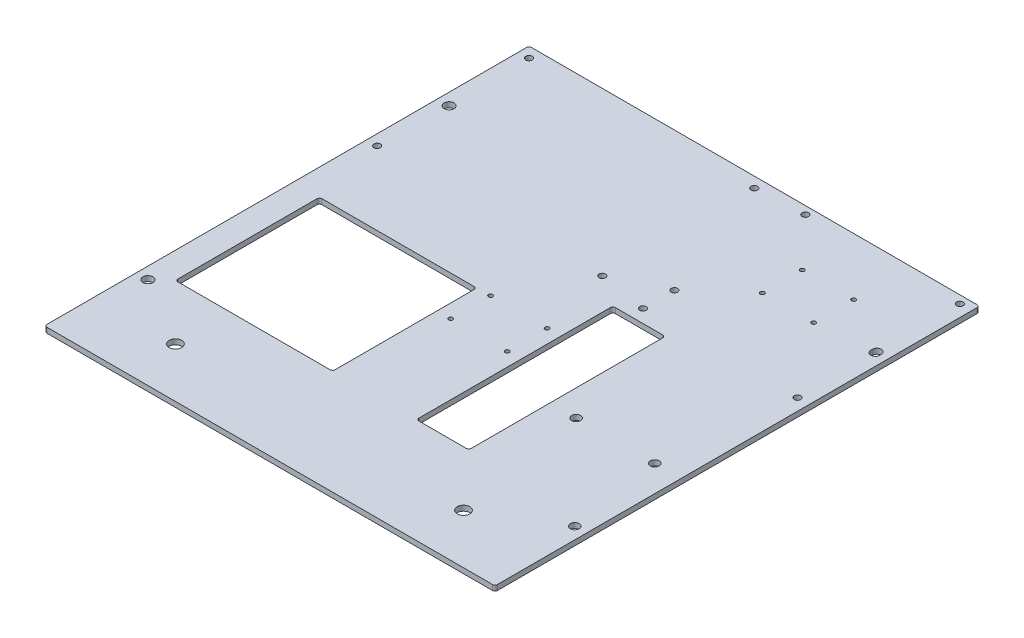
SolidWorks part; units mm, degrees
material "3.3535 (EN-AW 5154A)"
ref_plane "Ebene vorne" through (0, 0, 0) normal (0, 0, 1) x (1, 0, 0)
ref_plane "Ebene oben" through (0, 0, 0) normal (0, 1, 0) x (1, 0, 0)
ref_plane "Ebene rechts" through (0, 0, 0) normal (1, 0, 0) x (0, 0, -1)
sketch "Skizze1" plane through (0, 0, 0) normal (0, 1, 0) x (1, 0, 0)
  line L0 (-86, -92.5) -> (86, 92.5) construction
  line L1 (-86, 92.5) -> (86, 92.5)
  line L2 (-86, 92.5) -> (-86, -92.5)
  line L3 (-86, -92.5) -> (86, -92.5)
  line L4 (86, 92.5) -> (86, -92.5)
  point P4 (0, 0)
  dimension "D1" = 172
  dimension "D2" = 185
extrude "Aufsatz-Linear austragen1" add sketch "Skizze1" along normal blind 2
hole_wizard "Durchgangsloch für M31" positions "Skizze4" profile "Skizze3" hole size "M3" standard "ANSI Metrisch" end condition through all
sketch "Skizze4" plane through (0, 2, 0) normal (0, 1, 0) x (1, 0, 0)
  line L1 (-81.5, 57.5) -> (81.5, 57.5)
  line L2 (-81.5, 57.5) -> (-81.5, -57.5)
  line L3 (-81.5, -57.5) -> (81.5, -57.5)
  line L4 (81.5, 57.5) -> (81.5, -57.5)
  line L5 (86, 92.5) -> (-86, 92.5) construction
  line L6 (-86, -92.5) -> (86, -92.5) construction
  line L7 (-86, 92.5) -> (-86, -92.5) construction
  line L8 (86, -92.5) -> (86, 92.5) construction
  point P6 (81.5, -57.5)
  dimension "D1" = 35
  dimension "D2" = 35
  dimension "D3" = 4.5
  dimension "D4" = 4.5
sketch "Skizze3" plane through (81.5, 2, 57.5) normal (1, 0, 0) x (0, 0, 1)
  line L0 (0, 0) -> (0, 2)
  line L1 (0, 2) -> (1.7, 2)
  line L2 (1.7, 2) -> (1.7, 0)
  line L5 (1.7, 0) -> (0, 0)
  line L11 (0, -6.35) -> (0, 107.95) construction
  dimension "Bohrerdurchmesser" = 3.4
  dimension "Bohrungstiefe" = 2
hole_wizard "Ø3.8 (3.8) Durchmesser Bohrung1" positions "Skizze17" profile "Skizze18" hole size "Ø3.8" standard "ANSI Metrisch"
sketch "Skizze17" plane through (0, 2, 0) normal (0, 1, 0) x (1, 0, 0)
  point P0 (-81.5, -57.5)
  point P3 (-81.5, 57.5)
sketch "Skizze18" plane through (-81.5, 2, 57.5) normal (1, 0, 0) x (0, 0, 1)
  line L0 (0, 0) -> (0, 11.1416)
  line L1 (0, 11.1416) -> (1.9, 10)
  line L2 (1.9, 10) -> (1.9, 0)
  line L5 (1.9, 0) -> (0, 0)
  line L10 (0, 11.1416) -> (-1.9, 10) construction
  line L11 (0, -6.35) -> (0, 107.95) construction
  dimension "Bohrerdurchmesser" = 3.8
  dimension "Bohrungstiefe" = 10
  dimension "Spitzenwinkel" = 118
hole_wizard "Ø3.4 (3.4) Durchmesser Langloch1" positions "Skizze19" profile "Skizze21" size "Ø3.4" standard "ANSI Metrisch" slot yes end condition through all
sketch "Skizze19" plane through (0, 2, 0) normal (0, 1, 0) x (1, 0, 0)
  line L0 (81.5, 59.5) -> (81.5, 55.5) construction
  line L1 (81.5, 57.5) -> (81.5, -57.5) construction
  point P0 (81.5, 57.5)
  dimension "D1" = 4
sketch "Skizze21" plane through (81.5, 2, -57.5) normal (1, 0, 0) x (0, 0, 1)
  line L0 (0, 0) -> (0, 2)
  line L1 (0, 2) -> (1.7, 2)
  line L2 (1.7, 2) -> (1.7, 0)
  line L5 (1.7, 0) -> (0, 0)
  line L11 (0, -6.35) -> (0, 107.95) construction
  dimension "Bohrerdurchmesser" = 3.4
  dimension "Bohrungstiefe" = 2
sketch "Skizze5" plane through (0, 0, 0) normal (0, 1, 0) x (1, 0, 0)
  line L0 (-86, 92.5) -> (-86, -92.5) construction
  line L1 (16, 22.5) -> (36, 22.5)
  line L4 (36, 22.5) -> (36, -52.5)
  line L5 (-76, -52.5) -> (-16, -52.5)
  line L6 (-76, -52.5) -> (-76, 2.5)
  line L7 (-76, 2.5) -> (-16, 2.5)
  line L8 (-16, -52.5) -> (-16, 2.5)
  line L10 (86, 92.5) -> (-86, 92.5) construction
  line L11 (-86, -92.5) -> (86, -92.5) construction
  line L12 (16, 22.5) -> (16, -52.5)
  line L13 (16, -52.5) -> (36, -52.5)
  line L14 (86, -92.5) -> (86, 92.5) construction
  dimension "D1" = 50
  dimension "D2" = 20
  dimension "D3" = 10
  dimension "D5" = 70
  dimension "D6" = 90
  dimension "D7" = 40
  dimension "D8" = 60
extrude "Schnitt-Linear austragen1" cut sketch "Skizze5" along normal blind 10
hole_wizard "Ø4.3 (4.79) Durchmesser Bohrung1" positions "Skizze6" profile "Skizze7" hole size "Ø4.3" standard "ANSI Metrisch" end condition through all
sketch "Skizze6" plane through (0, 2, 0) normal (0, 1, 0) x (1, 0, 0)
  line L3 (-55, -73.5) -> (55, -73.5) construction
  point P0 (-55, -73.5)
  point P2 (55, -73.5)
  point P18 (0, -73.5)
  dimension "D1" = 73.5
  dimension "D2" = 110
sketch "Skizze7" plane through (-55, 2, 73.5) normal (1, 0, 0) x (0, 0, 1)
  line L0 (0, 0) -> (0, 2)
  line L1 (0, 2) -> (2.395, 2)
  line L2 (2.395, 2) -> (2.395, 0)
  line L5 (2.395, 0) -> (0, 0)
  line L11 (0, -6.35) -> (0, 107.95) construction
  dimension "Bohrerdurchmesser" = 4.79
  dimension "Bohrungstiefe" = 2
hole_wizard "Durchgangsloch für M32" positions "Skizze8" profile "Skizze9" hole size "M3" standard "ANSI Metrisch" end condition through all
sketch "Skizze8" plane through (0, 2, 0) normal (0, 1, 0) x (1, 0, 0)
  line L0 (46, -21.5) -> (76, -21.5)
  line L5 (-86, -92.5) -> (86, -92.5) construction
  line L6 (86, -92.5) -> (86, 92.5) construction
  point P0 (46, -21.5)
  point P2 (76, -21.5)
  dimension "D1" = 71
  dimension "D2" = 30
  dimension "D3" = 10
sketch "Skizze9" plane through (46, 2, 21.5) normal (1, 0, 0) x (0, 0, 1)
  line L0 (0, 0) -> (0, 2)
  line L1 (0, 2) -> (1.7, 2)
  line L2 (1.7, 2) -> (1.7, 0)
  line L5 (1.7, 0) -> (0, 0)
  line L11 (0, -6.35) -> (0, 107.95) construction
  dimension "Bohrerdurchmesser" = 3.4
  dimension "Bohrungstiefe" = 2
hole_wizard "M3x0.5 Gewindebohrung2" positions "Skizze10" profile "Skizze11" tap size "M3x0.5" standard "ANSI Metrisch" end condition through all
sketch "Skizze10" plane through (0, 2, 0) normal (0, 1, 0) x (1, 0, 0)
  line L1 (-82, 30.5) -> (4, 30.5)
  line L2 (-82, 30.5) -> (-82, 88.5)
  line L3 (-82, 88.5) -> (4, 88.5)
  line L4 (4, 30.5) -> (4, 88.5)
  line L5 (-86, 92.5) -> (-86, -92.5) construction
  line L6 (86, 92.5) -> (-86, 92.5) construction
  point P1 (-82, 30.5)
  point P2 (4, 88.5)
  point P45 (-82, 88.5)
  point P46 (4, 30.5)
  dimension "D1" = 58
  dimension "D2" = 86
  dimension "D3" = 4
  dimension "D4" = 4
sketch "Skizze11" plane through (-82, 2, -30.5) normal (1, 0, 0) x (0, 0, 1)
  line L0 (0, 0) -> (0, 2)
  line L1 (0, 2) -> (1.25, 2)
  line L2 (1.25, 2) -> (1.25, 0)
  line L5 (1.25, 0) -> (0, 0)
  line L11 (0, -6.35) -> (0, 107.95) construction
  dimension "Nenndurchmesser (Haupt)" = 2.5
  dimension "Bohrungstiefe" = 2
hole_wizard "M3x0.5 Gewindebohrung3" positions "Skizze12" profile "Skizze13" tap size "M3x0.5" standard "ANSI Metrisch" end condition through all
sketch "Skizze12" plane through (0, 2, 0) normal (0, 1, 0) x (1, 0, 0)
  line L1 (22.5, 27.5) -> (81.5, 27.5)
  line L2 (22.5, 27.5) -> (22.5, 89.5)
  line L3 (22.5, 89.5) -> (81.5, 89.5)
  line L4 (81.5, 27.5) -> (81.5, 89.5)
  line L5 (86, -92.5) -> (86, 92.5) construction
  line L6 (86, 92.5) -> (-86, 92.5) construction
  point P1 (22.5, 27.5)
  point P2 (81.5, 89.5)
  point P51 (22.5, 89.5)
  point P52 (81.5, 27.5)
  point P58 (22.5, 39.5)
  dimension "D1" = 62
  dimension "D2" = 59
  dimension "D3" = 4.5
  dimension "D4" = 3
  dimension "D5" = 12
sketch "Skizze13" plane through (22.5, 2, -27.5) normal (1, 0, 0) x (0, 0, 1)
  line L0 (0, 0) -> (0, 2)
  line L1 (0, 2) -> (1.25, 2)
  line L2 (1.25, 2) -> (1.25, 0)
  line L5 (1.25, 0) -> (0, 0)
  line L11 (0, -6.35) -> (0, 107.95) construction
  dimension "Nenndurchmesser (Haupt)" = 2.5
  dimension "Bohrungstiefe" = 2
fillet "Verrundung1" radius 1 12 edges at (36, 1, -22.5) (-16, 1, -2.5) (-16, 1, 52.5) (-76, 1, 52.5) (-76, 1, -2.5) (-86, 1, -92.5) (86, 1, -92.5) (-86, 1, 92.5) (86, 1, 92.5) (36, 1, 52.5) (16, 1, 52.5) (16, 1, -22.5)
sketch "Skizze14" plane through (0, 2, 0) normal (0, 1, 0) x (1, 0, 0)
  line L0 (-85, -92.5) -> (85, -92.5) construction
  line L1 (10.795, -12.62) -> (-10.795, -12.62)
  line L2 (10.795, -12.62) -> (10.795, 2.62)
  line L3 (10.795, 2.62) -> (-10.795, 2.62)
  line L4 (-10.795, -12.62) -> (-10.795, 2.62)
  point P4 (10.795, -5)
  point P7 (0, -12.62)
  point P8 (0, -92.5)
  dimension "D1" = 87.5
  dimension "D2" = 21.59
  dimension "D3" = 15.24
hole_wizard "M2x0.4 Gewindebohrung1" positions "Skizze15" profile "Skizze16" tap size "M2x0.4" standard "ANSI Metrisch" end condition through all
sketch "Skizze15" plane through (0, 2, 0) normal (0, 1, 0) x (1, 0, 0)
  line L1 (40.205, 55.38) -> (59.795, 55.38)
  line L2 (40.205, 55.38) -> (40.205, 70.62)
  line L3 (40.205, 70.62) -> (59.795, 70.62)
  line L4 (59.795, 55.38) -> (59.795, 70.62)
  point P0 (10.795, -12.62)
  point P3 (-10.795, -12.62)
  point P6 (-10.795, 2.62)
  point P9 (10.795, 2.62)
  point P42 (50, 55.38)
  point P43 (40.205, 63)
  point P46 (40.205, 70.62)
  point P49 (40.205, 55.38)
  point P52 (59.795, 55.38)
  point P55 (59.795, 70.62)
  dimension "D1" = 15.24
  dimension "D2" = 19.59
  dimension "D3" = 50
  dimension "D4" = 63
sketch "Skizze16" plane through (10.795, 2, 12.62) normal (1, 0, 0) x (0, 0, 1)
  line L0 (0, 0) -> (0, 2)
  line L1 (0, 2) -> (0.8, 2)
  line L2 (0.8, 2) -> (0.8, 0)
  line L5 (0.8, 0) -> (0, 0)
  line L11 (0, -6.35) -> (0, 107.95) construction
  dimension "Nenndurchmesser (Haupt)" = 1.6
  dimension "Bohrungstiefe" = 2
